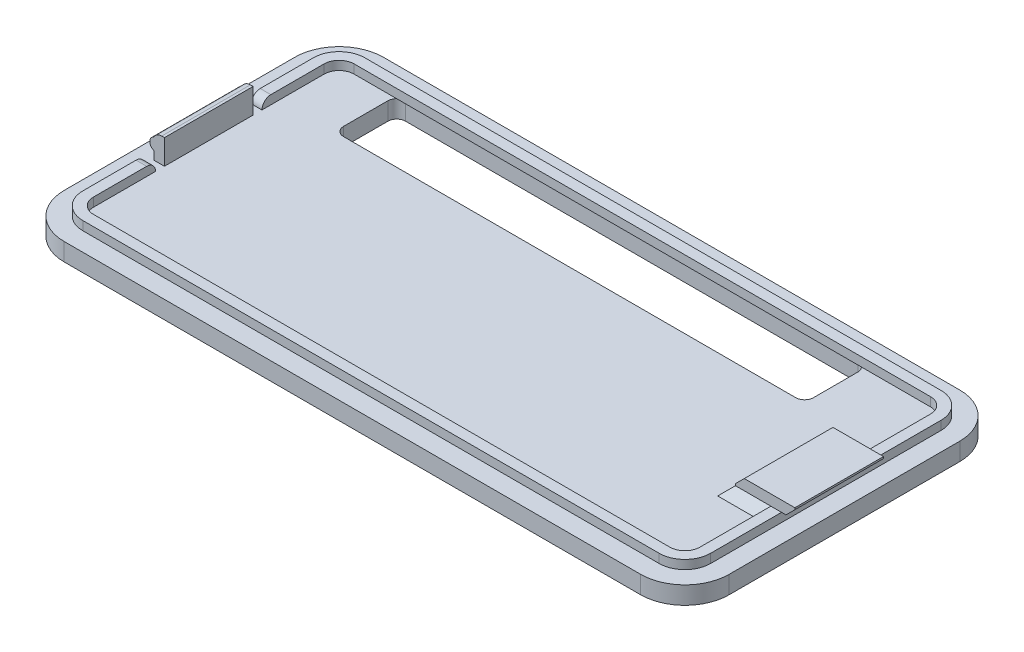
SolidWorks part; units mm, degrees
ref_plane "前视基准面" through (0, 0, 0) normal (0, 0, 1) x (1, 0, 0)
ref_plane "上视基准面" through (0, 0, 0) normal (0, 1, 0) x (1, 0, 0)
ref_plane "右视基准面" through (0, 0, 0) normal (1, 0, 0) x (0, 0, -1)
sketch "zero" plane through (0, 0, 0) normal (0, 1, 0) x (1, 0, 0)
  line L1 (-29.5, 15) -> (29.5, 15)
  line L2 (-32.5, 12) -> (-32.5, -12)
  line L3 (-29.5, -15) -> (29.5, -15)
  line L4 (32.5, 12) -> (32.5, -12)
  line L5 (-32.5, 15) -> (32.5, -15) construction
  line L6 (-32.5, -15) -> (32.5, 15) construction
  line L7 (-25.7, -15) -> (-14.5, -15)
  line L8 (-25.7, -15) -> (-25.7, -9.6569)
  line L9 (-25.7, -9.6569) -> (-14.5, -9.6569)
  line L10 (-14.5, -15) -> (-14.5, -9.6569)
  line L11 (5.2, -15) -> (12.7, -15)
  line L12 (5.2, -15) -> (5.2, -11)
  line L13 (5.2, -11) -> (12.7, -11)
  line L14 (12.7, -15) -> (12.7, -11)
  line L15 (17.8, -15) -> (25.3, -15)
  line L16 (17.8, -15) -> (17.8, -11)
  line L17 (17.8, -11) -> (25.3, -11)
  line L18 (25.3, -15) -> (25.3, -11)
  line L19 (-32.5, 7.7) -> (-19.5, 7.7)
  line L20 (-32.5, 7.7) -> (-32.5, -4.3)
  line L21 (-32.5, -4.3) -> (-19.5, -4.3)
  line L22 (-19.5, 7.7) -> (-19.5, -4.3)
  line L23 (-25.5, 14) -> (25.5, 14)
  line L24 (-25.5, 14) -> (-25.5, 8.8)
  line L25 (-25.5, 8.8) -> (25.5, 8.8)
  line L26 (25.5, 14) -> (25.5, 8.8)
  line L27 (-19.5, 7.2329) -> (-35.5, 7.2329)
  line L28 (-19.5, 7.2329) -> (-19.5, -3.7671)
  line L29 (-19.5, -3.7671) -> (-35.5, -3.7671)
  line L30 (-35.5, 7.2329) -> (-35.5, -3.7671)
  arc A0 (29.5, -15) -> (32.5, -12) centre (29.5, -12) ccw
  arc A1 (29.5, 15) -> (32.5, 12) centre (29.5, 12) cw
  arc A2 (-32.5, -12) -> (-29.5, -15) centre (-29.5, -12) ccw
  arc A3 (-29.5, 15) -> (-32.5, 12) centre (-29.5, 12) ccw
  circle A4 centre (-29, 11.4) radius 3
  circle A5 centre (-29, -11.5) radius 3
  circle A6 centre (29, 11.4) radius 3
  circle A7 centre (29, -11.5) radius 3
  circle A8 centre (-29, 11.4) radius 1.375
  circle A9 centre (-29, -11.5) radius 1.375
  circle A10 centre (29, -11.5) radius 1.375
  circle A11 centre (29, 11.4) radius 1.375
  point P0 (0, 0)
  dimension "D3" = 3
  dimension "D4" = 6
  dimension "D9" = 2.75
  dimension "D1" = 65
  dimension "D2" = 30
  dimension "D5" = 3.6
  dimension "D6" = 3.5
  dimension "D7" = 3.5
  dimension "D8" = 3.5
  dimension "D10" = 12
  dimension "D11" = 7.3
  dimension "D12" = 13
  dimension "D13" = 11.2
  dimension "D14" = 6.8
  dimension "D15" = 19.7
  dimension "D16" = 7.5
  dimension "D17" = 7.5
  dimension "D18" = 5.1
  dimension "D19" = 4
  dimension "D20" = 5.2
  dimension "D21" = 7
  dimension "D22" = 7
  dimension "D23" = 1
  dimension "D24" = 11
  dimension "D25" = 16
sketch "sugar" plane through (0, 0, 0) normal (0, 1, 0) x (1, 0, 0)
  line L1 (-29.5, 15) -> (29.5, 15)
  line L2 (-32.5, 12) -> (-32.5, -12)
  line L3 (-29.5, -15) -> (29.5, -15)
  line L4 (32.5, 12) -> (32.5, -12)
  line L5 (-32.5, 15) -> (32.5, -15) construction
  line L6 (-32.5, -15) -> (32.5, 15) construction
  line L7 (23.5, -11.5) -> (19.5, -11.5)
  line L8 (23.5, -11.5) -> (23.5, -13.9082)
  line L9 (23.5, -13.9082) -> (19.5, -13.9082)
  line L10 (19.5, -11.5) -> (19.5, -13.9082)
  line L11 (16, -11.0071) -> (8.5, -11.0071)
  line L12 (16, -11.0071) -> (16, -15)
  line L13 (16, -15) -> (8.5, -15)
  line L14 (8.5, -11.0071) -> (8.5, -15)
  line L15 (20.5, -13.9082) -> (22.5, -13.9082)
  line L16 (20.5, -13.9082) -> (20.5, -14.8173)
  line L17 (20.5, -14.8173) -> (22.5, -14.8173)
  line L18 (22.5, -13.9082) -> (22.5, -14.8173)
  arc A0 (29.5, 15) -> (32.5, 12) centre (29.5, 12) cw
  arc A1 (29.5, -15) -> (32.5, -12) centre (29.5, -12) ccw
  arc A2 (-32.5, -12) -> (-29.5, -15) centre (-29.5, -12) ccw
  arc A3 (-29.5, 15) -> (-32.5, 12) centre (-29.5, 12) ccw
  circle A4 centre (-29, 11.4) radius 3
  circle A5 centre (-29, 11.4) radius 1.375
  circle A6 centre (-29, -11.5) radius 3
  circle A7 centre (-29, -11.5) radius 1.375
  circle A8 centre (29, 11.4) radius 3
  circle A9 centre (29, 11.4) radius 1.375
  circle A10 centre (29, -11.5) radius 3
  circle A11 centre (29, -11.5) radius 1.375
  dimension "D3" = 3
  dimension "D1" = 65
  dimension "D2" = 30
  dimension "D4" = 9
  dimension "D5" = 4
  dimension "D6" = 3.5
  dimension "D7" = 7.5
  dimension "D8" = 2
  dimension "D9" = 1
sketch "case" plane through (0, 0, 0) normal (0, 1, 0) x (1, 0, 0)
  line L1 (-34.0422, 18) -> (30.9578, 18)
  line L2 (-39.0422, 13) -> (-39.0422, -13)
  line L3 (-34.0422, -18) -> (30.9578, -18)
  line L4 (35.9578, 13) -> (35.9578, -13)
  line L5 (-39.0422, 18) -> (35.9578, -18) construction
  line L6 (-39.0422, -18) -> (35.9578, 18) construction
  arc A0 (-39.0422, -13) -> (-34.0422, -18) centre (-34.0422, -13) ccw
  arc A1 (30.9578, -18) -> (35.9578, -13) centre (30.9578, -13) ccw
  arc A2 (30.9578, 18) -> (35.9578, 13) centre (30.9578, 13) cw
  arc A3 (-34.0422, 18) -> (-39.0422, 13) centre (-34.0422, 13) ccw
  point P0 (-1.5422, 0)
  point P3 (-1.5422, 0)
  dimension "D3" = 5
  dimension "D1" = 75
  dimension "D2" = 36
extrude "凸台-拉伸2" add sketch "case" along normal blind 2
sketch "草图2" plane through (0, 0, 0) normal (0, 1, 0) x (1, 0, 0)
  line L4 (-34.0422, -14.7) -> (30.9578, -14.7)
  line L5 (32.6578, -13) -> (32.6578, 13)
  line L6 (30.9578, 14.7) -> (-34.0422, 14.7)
  line L7 (-35.7422, 13) -> (-35.7422, -13)
  line L8 (33.8578, -13) -> (33.8578, 13)
  line L9 (30.9578, 15.9) -> (-34.0422, 15.9)
  line L10 (-36.9422, 13) -> (-36.9422, -13)
  line L11 (-34.0422, -15.9) -> (30.9578, -15.9)
  line L12 (33.8578, -13) -> (33.8578, 13)
  line L13 (30.9578, 15.9) -> (-34.0422, 15.9)
  line L14 (-36.9422, 13) -> (-36.9422, -13)
  line L15 (-34.0422, -15.9) -> (30.9578, -15.9)
  arc A4 (30.9578, -14.7) -> (32.6578, -13) centre (30.9578, -13) ccw
  arc A5 (32.6578, 13) -> (30.9578, 14.7) centre (30.9578, 13) ccw
  arc A6 (-34.0422, 14.7) -> (-35.7422, 13) centre (-34.0422, 13) ccw
  arc A7 (-35.7422, -13) -> (-34.0422, -14.7) centre (-34.0422, -13) ccw
  arc A8 (30.9578, -15.9) -> (33.8578, -13) centre (30.9578, -13) ccw
  arc A9 (33.8578, 13) -> (30.9578, 15.9) centre (30.9578, 13) ccw
  arc A10 (-34.0422, 15.9) -> (-36.9422, 13) centre (-34.0422, 13) ccw
  arc A11 (-36.9422, -13) -> (-34.0422, -15.9) centre (-34.0422, -13) ccw
  arc A12 (30.9578, -15.9) -> (33.8578, -13) centre (30.9578, -13) ccw
  arc A13 (33.8578, 13) -> (30.9578, 15.9) centre (30.9578, 13) ccw
  arc A14 (-34.0422, 15.9) -> (-36.9422, 13) centre (-34.0422, 13) ccw
  arc A15 (-36.9422, -13) -> (-34.0422, -15.9) centre (-34.0422, -13) ccw
  dimension "D1" = 2.1
  dimension "D2" = 1.2
ref_plane "基准面1" through (0, 2, 0) normal (0, 1, 0) x (1, 0, 0)
sketch "草图3" plane through (0, 2, 0) normal (0, 1, 0) x (1, 0, 0)
  line L4 (-34.0422, -14.7) -> (30.9578, -14.7)
  line L5 (32.6578, -13) -> (32.6578, 13)
  line L6 (30.9578, 14.7) -> (-34.0422, 14.7)
  line L7 (-35.7422, 13) -> (-35.7422, -13)
  line L8 (-34.0422, -14.7) -> (30.9578, -14.7)
  line L9 (32.6578, -13) -> (32.6578, 13)
  line L10 (30.9578, 14.7) -> (-34.0422, 14.7)
  line L11 (-35.7422, 13) -> (-35.7422, -13)
  line L12 (-36.9422, 13) -> (-36.9422, -13)
  line L13 (-34.0422, -15.9) -> (30.9578, -15.9)
  line L14 (33.8578, -13) -> (33.8578, 13)
  line L15 (30.9578, 15.9) -> (-34.0422, 15.9)
  line L16 (-36.9422, 13) -> (-36.9422, -13)
  line L17 (-34.0422, -15.9) -> (30.9578, -15.9)
  line L18 (33.8578, -13) -> (33.8578, 13)
  line L19 (30.9578, 15.9) -> (-34.0422, 15.9)
  arc A4 (30.9578, -14.7) -> (32.6578, -13) centre (30.9578, -13) ccw
  arc A5 (32.6578, 13) -> (30.9578, 14.7) centre (30.9578, 13) ccw
  arc A6 (-34.0422, 14.7) -> (-35.7422, 13) centre (-34.0422, 13) ccw
  arc A7 (-35.7422, -13) -> (-34.0422, -14.7) centre (-34.0422, -13) ccw
  arc A8 (30.9578, -14.7) -> (32.6578, -13) centre (30.9578, -13) ccw
  arc A9 (32.6578, 13) -> (30.9578, 14.7) centre (30.9578, 13) ccw
  arc A10 (-34.0422, 14.7) -> (-35.7422, 13) centre (-34.0422, 13) ccw
  arc A11 (-35.7422, -13) -> (-34.0422, -14.7) centre (-34.0422, -13) ccw
  arc A12 (-36.9422, -13) -> (-34.0422, -15.9) centre (-34.0422, -13) ccw
  arc A13 (30.9578, -15.9) -> (33.8578, -13) centre (30.9578, -13) ccw
  arc A14 (33.8578, 13) -> (30.9578, 15.9) centre (30.9578, 13) ccw
  arc A15 (-34.0422, 15.9) -> (-36.9422, 13) centre (-34.0422, 13) ccw
  arc A16 (-36.9422, -13) -> (-34.0422, -15.9) centre (-34.0422, -13) ccw
  arc A17 (30.9578, -15.9) -> (33.8578, -13) centre (30.9578, -13) ccw
  arc A18 (33.8578, 13) -> (30.9578, 15.9) centre (30.9578, 13) ccw
  arc A19 (-34.0422, 15.9) -> (-36.9422, 13) centre (-34.0422, 13) ccw
  dimension "D1" = 0
  dimension "D2" = 0
extrude "凸台-拉伸4" add sketch "草图3" along normal blind 1
sketch "草图5" plane through (0, 2, 0) normal (0, 1, 0) x (1, 0, 0)
  line L0 (32.6578, -13) -> (32.6578, 13) construction
  line L1 (28.6578, 5) -> (32.6578, 5)
  line L2 (28.6578, 5) -> (28.6578, -5)
  line L3 (28.6578, -5) -> (32.6578, -5)
  line L4 (32.6578, 5) -> (32.6578, -5)
  line L5 (28.6578, 5) -> (32.6578, -5) construction
  line L6 (28.6578, -5) -> (32.6578, 5) construction
  point P0 (30.6578, 0)
  dimension "D2" = 10
  dimension "D3" = 4
  dimension "D4" = 0
extrude "凸台-拉伸6" add sketch "草图5" along normal blind 2.2
ref_plane "基准面3" through (33.8578, 0, 0) normal (1, 0, 0) x (0, 0, -1)
ref_plane "基准面4" through (32.6578, 0, 0) normal (1, 0, 0) x (0, 0, -1)
sketch "草图6" plane through (32.6578, 0, 0) normal (1, 0, 0) x (0, 0, -1)
  line L1 (5, 4.2) -> (-5, 4.2)
  line L2 (5, 4.2) -> (5, 3)
  line L3 (5, 3) -> (-5, 3)
  line L4 (-5, 4.2) -> (-5, 3)
extrude "凸台-拉伸7" add sketch "草图6" along normal blind 2.7
chamfer "倒角1" distance 1 angle 45 1 edges at (35.3578, 3, 0)
chamfer "倒角2" distance 1 angle 45 3 edges at (30.6578, 2, 5) (28.6578, 2, 0) (30.6578, 2, -5)
chamfer "倒角3" distance 1 angle 45 1 edges at (28.6578, 4.2, 0)
sketch "草图7" plane through (0, 2, 0) normal (0, 1, 0) x (1, 0, 0)
  line L0 (-36.9422, 13) -> (-36.9422, -13) construction
  line L1 (-36.9422, 5) -> (-35.7422, 5)
  line L2 (-36.9422, 5) -> (-36.9422, -5)
  line L3 (-36.9422, -5) -> (-35.7422, -5)
  line L4 (-35.7422, 5) -> (-35.7422, -5)
  line L5 (-35.7422, 13) -> (-35.7422, -13) construction
  point P10 (-35.7422, 0)
  dimension "D1" = 5
  dimension "D2" = 10
extrude "凸台-拉伸8" add sketch "草图7" along normal blind 2.8
ref_plane "基准面5" through (0, 0, 5) normal (0, 0, 1) x (1, 0, 0)
sketch "草图8" plane through (0, 0, 5) normal (0, 0, 1) x (1, 0, 0)
  line L0 (-34.0422, 2) -> (-39.0422, 2) construction
  line L1 (-36.9422, 4.8) -> (-36.9422, 3) construction
  circle A0 centre (-36.6922, 3.6) radius 0.7
  dimension "D1" = 1.4
  dimension "D2" = 1.6
  dimension "D3" = 0.25
extrude "凸台-拉伸9" add sketch "草图8" against normal blind 10
fillet "圆角1" radius 1 1 edges at (-36.9422, 4.8, 0)
ref_plane "基准面7" through (-36.9422, 0, 0) normal (-1, 0, 0) x (0, 0, 1)
sketch "草图11" plane through (-36.9422, 0, 0) normal (-1, 0, 0) x (0, 0, 1)
  line L0 (-13, 2) -> (13, 2) construction
  line L1 (5, 3) -> (6, 3)
  line L2 (5, 3) -> (5, 2)
  line L3 (5, 2) -> (6, 2)
  line L4 (6, 3) -> (6, 2)
  line L6 (-5, 3) -> (-6, 3)
  line L7 (-5, 3) -> (-5, 2)
  line L8 (-5, 2) -> (-6, 2)
  line L9 (-6, 3) -> (-6, 2)
  dimension "D1" = 1
  dimension "D2" = 1
extrude "切除-拉伸1" cut sketch "草图11" against normal blind 1.2
fillet "圆角2" radius 1 2 edges at (-36.3422, 3, 6) (-36.3422, 3, -6)
ref_plane "基准面8" through (0, 0, 0) normal (0, -1, 0) x (-1, 0, 0)
sketch "草图12" plane through (0, 0, 0) normal (0, -1, 0) x (-1, 0, 0)
  line L76 (34.0422, -18) -> (-30.9578, -18) construction
  line L78 (39.0422, 13) -> (39.0422, -13) construction
  line B0 (-8.1993, 1.426) -> (-9.0198, 1.899)
  line B1 (-9.0198, 1.899) -> (-13.2767, 4.3551)
  line B2 (-13.2767, 4.3551) -> (-14.0973, 4.8339)
  line B3 (-15.8183, 4.8339) -> (-16.6389, 4.3551)
  line B4 (-16.6389, 4.3551) -> (-20.8958, 1.899)
  line B5 (-20.8958, 1.899) -> (-21.7165, 1.426)
  line B6 (-22.577, -0.0613) -> (-22.577, -6.8769)
  line B7 (-21.7165, -8.3643) -> (-20.8958, -8.8373)
  line B8 (-20.8958, -8.8373) -> (-16.6389, -11.2934)
  line B9 (-16.6389, -11.2934) -> (-15.8183, -11.772)
  line B10 (-14.0973, -11.772) -> (-13.2767, -11.2934)
  line B11 (-13.2767, -11.2934) -> (-9.0198, -8.8373)
  line B12 (-9.0198, -8.8373) -> (-8.1993, -8.3643)
  line B13 (-7.3388, -6.8769) -> (-7.3388, -0.0613)
  line B14 (-20.6223, 0.7479) -> (-15.3568, 3.791)
  line B15 (-14.5532, 3.791) -> (-9.3162, 0.7422)
  line B16 (-9.3105, 0.0413) -> (-14.3993, -3.0018)
  line B17 (-12.8208, -8.1591) -> (-13.4135, -8.4896)
  line B18 (-13.4705, -8.5865) -> (-13.4705, -10.2961)
  line B19 (-13.5274, -10.393) -> (-14.633, -11.0198)
  line B20 (-14.7983, -10.9229) -> (-14.7983, -5.646)
  line B21 (-14.7413, -5.5491) -> (-12.8607, -4.4835)
  line B22 (-8.9173, -7.8058) -> (-10.0114, -8.4269)
  line B23 (-10.1767, -8.3301) -> (-10.1767, -5.8169)
  line B24 (-10.1197, -5.7201) -> (-9.0256, -5.1046)
  line B25 (-8.8603, -5.2015) -> (-8.8603, -7.7089)
  line B26 (-12.8893, -7.1447) -> (-13.4135, -7.4069)
  line B27 (-13.4705, -7.2872) -> (-13.4705, -5.9423)
  line B28 (-13.4135, -5.8455) -> (-12.9234, -5.5719)
  line B29 (-3.344, -0.54) -> (-5.2189, -0.54)
  line B30 (-5.2189, -0.54) -> (-5.2189, -7.1048)
  line B31 (-5.2189, -7.1048) -> (-4.3868, -7.1048)
  line B32 (-4.3868, -7.1048) -> (-4.3868, -4.5005)
  line B33 (-4.3868, -4.5005) -> (-3.2984, -4.5005)
  line B34 (-3.4066, -3.8281) -> (-4.3868, -3.8281)
  line B35 (-4.3868, -3.8281) -> (-4.3868, -1.2124)
  line B36 (-4.3868, -1.2124) -> (-3.4408, -1.2124)
  line B37 (0.1948, -2.2382) -> (0.1948, -7.1048)
  line B38 (0.1948, -7.1048) -> (1.0098, -7.1048)
  line B39 (1.0098, -7.1048) -> (1.0098, -2.2382)
  line B40 (1.0098, -2.2382) -> (0.1948, -2.2382)
  line B41 (5.7169, -3.3153) -> (4.8849, -2.9847)
  line B42 (6.0417, -2.1983) -> (6.8396, -1.1953)
  line B43 (3.6084, -4.1586) -> (4.4575, -4.5177)
  line B44 (2.9074, -5.1673) -> (2.0014, -6.2729)
  line B45 (10.8229, -2.0102) -> (10.8229, -5.3497)
  line B46 (9.3811, -4.9621) -> (9.3811, -2.0102)
  line B47 (9.3811, -2.0102) -> (7.7912, -2.0102)
  line B48 (7.7912, -2.0102) -> (7.7912, -5.1616)
  line B49 (10.9711, -6.4039) -> (11.0052, -6.4039)
  line B50 (11.0052, -6.4039) -> (11.1193, -7.1048)
  line B51 (11.1193, -7.1048) -> (12.4185, -7.1048)
  line B52 (12.4185, -7.1048) -> (12.4185, -2.0102)
  line B53 (12.4185, -2.0102) -> (10.8229, -2.0102)
  line B54 (16.2708, -6.1019) -> (15.4673, -6.1019)
  line B55 (17.365, -3.1614) -> (18.1513, -3.1614)
  line B56 (18.1513, -3.1614) -> (18.1513, -2.0102)
  line B57 (18.1513, -2.0102) -> (16.2822, -2.0102)
  line B58 (14.0312, -5.0533) -> (14.0312, -5.0875)
  line B59 (13.9344, -6.9168) -> (13.9344, -6.9624)
  line B60 (15.4844, -7.3214) -> (15.9688, -7.3214)
  line B61 (18.6072, -2.5516) -> (19.1657, -3.6002)
  line B62 (21.411, -6.592) -> (21.4508, -6.592)
  line B63 (21.4508, -6.592) -> (21.5648, -7.1048)
  line B64 (21.5648, -7.1048) -> (22.8641, -7.1048)
  line B65 (22.8641, -7.1048) -> (22.8641, -4.2099)
  line B66 (21.2685, -4.7741) -> (21.2685, -5.589)
  line B67 (25.3545, -2.8935) -> (25.3203, -2.8935)
  line B68 (25.3203, -2.8935) -> (25.212, -2.0102)
  line B69 (25.212, -2.0102) -> (23.9127, -2.0102)
  line B70 (23.9127, -2.0102) -> (23.9127, -7.1048)
  line B71 (23.9127, -7.1048) -> (25.4969, -7.1048)
  line B72 (25.4969, -7.1048) -> (25.4969, -4.1928)
  line B73 (27.1552, -3.3608) -> (27.423, -1.9875)
  line B74 (-13.4135, -7.4069) -> (-13.4135, -8.4896)
  line B75 (-13.4705, -7.2872) -> (-13.4705, -8.5865)
  spline B76 degree 3 poles (-14.0973, 4.8339) (-14.3652, 4.982) (-14.6615, 5.0618) (-14.9578, 5.0618) knots 3 3 3 3 4 4 4 4
  spline B77 degree 3 poles (-14.9578, 5.0618) (-15.2541, 5.0618) (-15.5505, 4.982) (-15.8183, 4.8339) knots 4 4 4 4 5 5 5 5
  spline B78 degree 3 poles (-21.7165, 1.426) (-22.2464, 1.1183) (-22.577, 0.5485) (-22.577, -0.0613) knots 8 8 8 8 9 9 9 9
  spline B79 degree 3 poles (-22.577, -6.8769) (-22.577, -7.4923) (-22.2464, -8.0565) (-21.7165, -8.3643) knots 10 10 10 10 11 11 11 11
  spline B80 degree 3 poles (-15.8183, -11.772) (-15.5505, -11.9259) (-15.2541, -12) (-14.9578, -12) knots 14 14 14 14 15 15 15 15
  spline B81 degree 3 poles (-14.9578, -12) (-14.6615, -12) (-14.3652, -11.9259) (-14.0973, -11.772) knots 15 15 15 15 16 16 16 16
  spline B82 degree 3 poles (-8.1993, -8.3643) (-7.6636, -8.0565) (-7.3388, -7.4923) (-7.3388, -6.8769) knots 19 19 19 19 20 20 20 20
  spline B83 degree 3 poles (-7.3388, -0.0613) (-7.3388, 0.5485) (-7.6636, 1.1183) (-8.1993, 1.426) knots 21 21 21 21 22 22 22 22
  spline B84 degree 2 poles (-15.5106, -3.0018) (-20.6622, -0.0271) (-20.6736, -0.0214) knots 0 0 0 1 1 1
  spline B85 degree 3 poles (-20.6736, -0.0214) (-20.9414, 0.1723) (-20.9129, 0.5826) (-20.6223, 0.7479) knots 1 1 1 1 2 2 2 2
  spline B86 degree 3 poles (-15.3568, 3.791) (-15.1117, 3.9335) (-14.8039, 3.9335) (-14.5532, 3.791) knots 3 3 3 3 4 4 4 4
  spline B87 degree 3 poles (-9.3162, 0.7422) (-9.0484, 0.5883) (-9.0427, 0.2008) (-9.3105, 0.0413) knots 5 5 5 5 6 6 6 6
  spline B88 degree 3 poles (-14.3993, -3.0018) (-14.7413, -3.2013) (-15.1687, -3.2013) (-15.5106, -3.0018) knots 7 7 7 7 8 8 8 8
  spline B89 degree 3 poles (-13.4705, -10.2961) (-13.4705, -10.336) (-13.4876, -10.3702) (-13.5274, -10.393) knots 3 3 3 3 4 4 4 4
  spline B90 degree 3 poles (-14.633, -11.0198) (-14.7071, -11.0597) (-14.7983, -11.0084) (-14.7983, -10.9229) knots 5 5 5 5 6 6 6 6
  spline B91 degree 3 poles (-14.7983, -5.646) (-14.7983, -5.6061) (-14.7812, -5.5662) (-14.7413, -5.5491) knots 7 7 7 7 8 8 8 8
  spline B92 degree 3 poles (-12.8607, -4.4835) (-11.6412, -3.7939) (-10.6326, -3.6572) (-10.6326, -5.0249) knots 9 9 9 9 10 10 10 10
  spline B93 degree 3 poles (-10.6326, -5.0249) (-10.6326, -6.3412) (-11.6526, -7.498) (-12.8208, -8.1591) knots 10 10 10 10 11 11 11 11
  spline B94 degree 3 poles (-8.8603, -7.7089) (-8.8603, -7.7488) (-8.8831, -7.7887) (-8.9173, -7.8058) knots 0 0 0 0 1 1 1 1
  spline B95 degree 3 poles (-10.0114, -8.4269) (-10.0855, -8.4668) (-10.1767, -8.4155) (-10.1767, -8.3301) knots 2 2 2 2 3 3 3 3
  spline B96 degree 3 poles (-10.1767, -5.8169) (-10.1767, -5.7771) (-10.1539, -5.7429) (-10.1197, -5.7201) knots 4 4 4 4 5 5 5 5
  spline B97 degree 3 poles (-9.0256, -5.1046) (-8.9515, -5.0647) (-8.8603, -5.116) (-8.8603, -5.2015) knots 6 6 6 6 7 7 7 7
  spline B98 degree 3 poles (-9.5156, -3.4349) (-9.0768, -3.1842) (-8.7634, -3.2924) (-8.7634, -3.6914) (-8.7634, -4.0846) (-9.0768, -4.5461) (-9.5156, -4.7912) knots 2 2 2 2 3 3 3 4 4 4 4
  spline B99 degree 3 poles (-9.5156, -4.7912) (-9.9601, -5.0476) (-10.2735, -4.9394) (-10.2735, -4.5461) (-10.2735, -4.1415) (-9.9601, -3.6856) (-9.5156, -3.4349) knots 0 0 0 0 1 1 1 2 2 2 2
  spline B100 degree 3 poles (-11.9319, -5.76) (-11.9319, -6.3013) (-12.2395, -6.78) (-12.8893, -7.1447) knots 0 0 0 0 1 1 1 1
  spline B101 degree 3 poles (-13.4705, -5.9423) (-13.4705, -5.9024) (-13.4477, -5.8625) (-13.4135, -5.8455) knots 4 4 4 4 5 5 5 5
  spline B102 degree 3 poles (-12.9234, -5.5719) (-12.2852, -5.2072) (-11.9319, -5.2015) (-11.9319, -5.76) knots 6 6 6 6 7 7 7 7
  spline B103 degree 3 poles (-3.2984, -4.5005) (-1.868, -4.5005) (-0.8822, -3.8509) (-0.8822, -2.4661) knots 5 5 5 5 6 6 6 6
  spline B104 degree 3 poles (-0.8822, -2.4661) (-0.8822, -1.0301) (-1.868, -0.54) (-3.344, -0.54) knots 6 6 6 6 7 7 7 7
  spline B105 degree 3 poles (-3.4408, -1.2124) (-2.2897, -1.2124) (-1.7084, -1.5145) (-1.7084, -2.4661) knots 3 3 3 3 4 4 4 4
  spline B106 degree 3 poles (-1.7084, -2.4661) (-1.7084, -3.4064) (-2.2498, -3.8281) (-3.4066, -3.8281) knots 4 4 4 4 5 5 5 5
  spline B107 degree 3 poles (0.6052, -1.2352) (0.93, -1.2352) (1.1694, -1.013) (1.1694, -0.711) (1.1694, -0.3747) (0.93, -0.181) (0.6052, -0.181) knots 2 2 2 2 3 3 3 4 4 4 4
  spline B108 degree 3 poles (0.6052, -0.181) (0.2804, -0.181) (0.041, -0.3747) (0.041, -0.711) (0.041, -1.013) (0.2804, -1.2352) (0.6052, -1.2352) knots 0 0 0 0 1 1 1 2 2 2 2
  spline B109 degree 3 poles (4.8849, -2.9847) (4.2979, -2.7511) (3.8762, -2.6086) (3.8762, -2.2382) knots 1 1 1 1 2 2 2 2
  spline B110 degree 3 poles (3.8762, -2.2382) (3.8762, -1.8849) (4.1783, -1.6854) (4.674, -1.6854) knots 2 2 2 2 3 3 3 3
  spline B111 degree 3 poles (4.674, -1.6854) (5.1926, -1.6854) (5.6029, -1.8621) (6.0417, -2.1983) knots 3 3 3 3 4 4 4 4
  spline B112 degree 3 poles (6.8396, -1.1953) (6.2583, -0.6084) (5.4433, -0.3121) (4.674, -0.3121) knots 5 5 5 5 6 6 6 6
  spline B113 degree 3 poles (4.674, -0.3121) (3.2551, -0.3121) (2.2521, -1.2124) (2.2521, -2.3294) knots 6 6 6 6 7 7 7 7
  spline B114 degree 3 poles (2.2521, -2.3294) (2.2521, -3.2981) (2.9074, -3.8794) (3.6084, -4.1586) knots 7 7 7 7 8 8 8 8
  spline B115 degree 3 poles (4.4575, -4.5177) (5.0274, -4.757) (5.3978, -4.8824) (5.3978, -5.2699) knots 9 9 9 9 10 10 10 10
  spline B116 degree 3 poles (5.3978, -5.2699) (5.3978, -5.6289) (5.1185, -5.8511) (4.5259, -5.8511) knots 10 10 10 10 11 11 11 11
  spline B117 degree 3 poles (4.5259, -5.8511) (4.0016, -5.8511) (3.3804, -5.5719) (2.9074, -5.1673) knots 11 11 11 11 12 12 12 12
  spline B118 degree 3 poles (2.0014, -6.2729) (2.6909, -6.9054) (3.6254, -7.2302) (4.4916, -7.2302) knots 13 13 13 13 14 14 14 14
  spline B119 degree 3 poles (4.4916, -7.2302) (6.1044, -7.2302) (7.0389, -6.2557) (7.0389, -5.1445) knots 14 14 14 14 15 15 15 15
  spline B120 degree 3 poles (7.0389, -5.1445) (7.0389, -4.2042) (6.5432, -3.6458) (5.7169, -3.3153) knots 15 15 15 15 16 16 16 16
  spline B121 degree 3 poles (10.8229, -5.3497) (10.5551, -5.7258) (10.3328, -5.8682) (9.9738, -5.8682) knots 1 1 1 1 2 2 2 2
  spline B122 degree 3 poles (9.9738, -5.8682) (9.5692, -5.8682) (9.3811, -5.6688) (9.3811, -4.9621) knots 2 2 2 2 3 3 3 3
  spline B123 degree 3 poles (7.7912, -5.1616) (7.7912, -6.4324) (8.2642, -7.2302) (9.3754, -7.2302) knots 6 6 6 6 7 7 7 7
  spline B124 degree 3 poles (9.3754, -7.2302) (10.0706, -7.2302) (10.5494, -6.9054) (10.9711, -6.4039) knots 7 7 7 7 8 8 8 8
  spline B125 degree 3 poles (15.4673, -6.1019) (14.9202, -6.1019) (14.7151, -5.9936) (14.7151, -5.76) knots 1 1 1 1 2 2 2 2
  spline B126 degree 3 poles (14.7151, -5.76) (14.7151, -5.589) (14.7549, -5.5092) (14.8746, -5.4009) knots 2 2 2 2 3 3 3 3
  spline B127 degree 3 poles (14.8746, -5.4009) (15.0969, -5.4636) (15.302, -5.4921) (15.473, -5.4921) knots 3 3 3 3 4 4 4 4
  spline B128 degree 3 poles (15.473, -5.4921) (16.6013, -5.4921) (17.5074, -4.9735) (17.5074, -3.7825) knots 4 4 4 4 5 5 5 5
  spline B129 degree 3 poles (17.5074, -3.7825) (17.5074, -3.5375) (17.4447, -3.3038) (17.365, -3.1614) knots 5 5 5 5 6 6 6 6
  spline B130 degree 3 poles (16.2822, -2.0102) (16.0485, -1.9248) (15.7693, -1.8849) (15.473, -1.8849) knots 9 9 9 9 10 10 10 10
  spline B131 degree 3 poles (15.473, -1.8849) (14.3732, -1.8849) (13.3417, -2.4889) (13.3417, -3.7369) knots 10 10 10 10 11 11 11 11
  spline B132 degree 3 poles (13.3417, -3.7369) (13.3417, -4.3296) (13.6722, -4.8026) (14.0312, -5.0533) knots 11 11 11 11 12 12 12 12
  spline B133 degree 3 poles (14.0312, -5.0875) (13.7007, -5.3212) (13.467, -5.6802) (13.467, -6.0392) knots 13 13 13 13 14 14 14 14
  spline B134 degree 3 poles (13.467, -6.0392) (13.467, -6.4666) (13.6665, -6.7344) (13.9344, -6.9168) knots 14 14 14 14 15 15 15 15
  spline B135 degree 3 poles (13.9344, -6.9624) (13.4613, -7.2017) (13.2106, -7.5436) (13.2106, -7.9653) knots 16 16 16 16 17 17 17 17
  spline B136 degree 3 poles (13.2106, -7.9653) (13.2106, -8.8771) (14.1737, -9.2475) (15.3476, -9.2475) knots 17 17 17 17 18 18 18 18
  spline B137 degree 3 poles (15.3476, -9.2475) (17.1199, -9.2475) (18.2312, -8.4839) (18.2312, -7.4069) knots 18 18 18 18 19 19 19 19
  spline B138 degree 3 poles (18.2312, -7.4069) (18.2312, -6.4837) (17.5245, -6.1019) (16.2708, -6.1019) knots 19 19 19 19 20 20 20 20
  spline B139 degree 3 poles (15.473, -4.5347) (15.1083, -4.5347) (14.8291, -4.2669) (14.8291, -3.7369) (14.8291, -3.2184) (15.1083, -2.9505) (15.473, -2.9505) knots 2 2 2 2 3 3 3 4 4 4 4
  spline B140 degree 3 poles (15.473, -2.9505) (15.8491, -2.9505) (16.1169, -3.2184) (16.1169, -3.7369) (16.1169, -4.2669) (15.8491, -4.5347) (15.473, -4.5347) knots 0 0 0 0 1 1 1 2 2 2 2
  spline B141 degree 3 poles (15.5983, -8.2503) (14.943, -8.2503) (14.5156, -8.0736) (14.5156, -7.7146) knots 0 0 0 0 1 1 1 1
  spline B142 degree 3 poles (14.5156, -7.7146) (14.5156, -7.5436) (14.5953, -7.4012) (14.7549, -7.2587) knots 1 1 1 1 2 2 2 2
  spline B143 degree 3 poles (14.7549, -7.2587) (14.9202, -7.3043) (15.114, -7.3214) (15.4844, -7.3214) knots 2 2 2 2 3 3 3 3
  spline B144 degree 3 poles (15.9688, -7.3214) (16.4417, -7.3214) (16.7096, -7.3841) (16.7096, -7.6861) knots 4 4 4 4 5 5 5 5
  spline B145 degree 3 poles (16.7096, -7.6861) (16.7096, -8.0109) (16.2537, -8.2503) (15.5983, -8.2503) knots 5 5 5 5 6 6 6 6
  spline B146 degree 3 poles (20.8013, -1.8849) (20.0091, -1.8849) (19.2797, -2.1527) (18.6072, -2.5516) knots 0 0 0 0 1 1 1 1
  spline B147 degree 3 poles (19.1657, -3.6002) (19.6729, -3.3153) (20.0946, -3.1557) (20.4992, -3.1557) knots 2 2 2 2 3 3 3 3
  spline B148 degree 3 poles (20.4992, -3.1557) (21.0177, -3.1557) (21.2344, -3.395) (21.2685, -3.8053) knots 3 3 3 3 4 4 4 4
  spline B149 degree 3 poles (21.2685, -3.8053) (19.2797, -4.0219) (18.4362, -4.6031) (18.4362, -5.6802) knots 4 4 4 4 5 5 5 5
  spline B150 degree 3 poles (18.4362, -5.6802) (18.4362, -6.5293) (19.0118, -7.2302) (19.9522, -7.2302) knots 5 5 5 5 6 6 6 6
  spline B151 degree 3 poles (19.9522, -7.2302) (20.5163, -7.2302) (20.9893, -6.9681) (21.411, -6.592) knots 6 6 6 6 7 7 7 7
  spline B152 degree 3 poles (22.8641, -4.2099) (22.8641, -2.6143) (22.1176, -1.8849) (20.8013, -1.8849) knots 11 11 11 11 12 12 12 12
  spline B153 degree 3 poles (21.2685, -5.589) (21.0349, -5.8398) (20.824, -5.9936) (20.4992, -5.9936) knots 0 0 0 0 1 1 1 1
  spline B154 degree 3 poles (20.4992, -5.9936) (20.1686, -5.9936) (19.9522, -5.8511) (19.9522, -5.5548) knots 1 1 1 1 2 2 2 2
  spline B155 degree 3 poles (19.9522, -5.5548) (19.9522, -5.1958) (20.277, -4.9109) (21.2685, -4.7741) knots 2 2 2 2 3 3 3 3
  spline B156 degree 3 poles (26.8076, -1.8849) (26.2947, -1.8849) (25.7305, -2.2154) (25.3545, -2.8935) knots 0 0 0 0 1 1 1 1
  spline B157 degree 3 poles (25.4969, -4.1928) (25.7648, -3.5204) (26.2207, -3.2811) (26.5967, -3.2811) knots 7 7 7 7 8 8 8 8
  spline B158 degree 3 poles (26.5967, -3.2811) (26.8247, -3.2811) (26.9729, -3.3153) (27.1552, -3.3608) knots 8 8 8 8 9 9 9 9
  spline B159 degree 3 poles (27.423, -1.9875) (27.2806, -1.9248) (27.1096, -1.8849) (26.8076, -1.8849) knots 10 10 10 10 11 11 11 11
  dimension "D1" = 6
  dimension "D2" = 54
sketch_block_instance "块1-1"
sketch_block "块1"
extrude "切除-拉伸2" cut sketch "草图12" against normal blind 0.5
sketch "草图13" plane through (0, 0, 0) normal (0, 1, 0) x (1, 0, 0)
  line L0 (30.9578, 18) -> (-34.0422, 18) construction
  line L1 (-29.5422, 15) -> (23.4578, 15)
  line L2 (-29.5422, 15) -> (-29.5422, 8)
  line L3 (-29.5422, 8) -> (23.4578, 8)
  line L4 (23.4578, 15) -> (23.4578, 8)
  line L6 (-39.0422, 13) -> (-39.0422, -13) construction
  point P6 (0, 0)
  dimension "D1" = 7
  dimension "D2" = 53
  dimension "D3" = 3
  dimension "D4" = 9.5
extrude "切除-拉伸3" cut sketch "草图13" along normal blind 2
fillet "圆角3" radius 1 4 edges at (-29.5422, 1, -15) (-29.5422, 1, -8) (23.4578, 1, -15) (23.4578, 1, -8)
